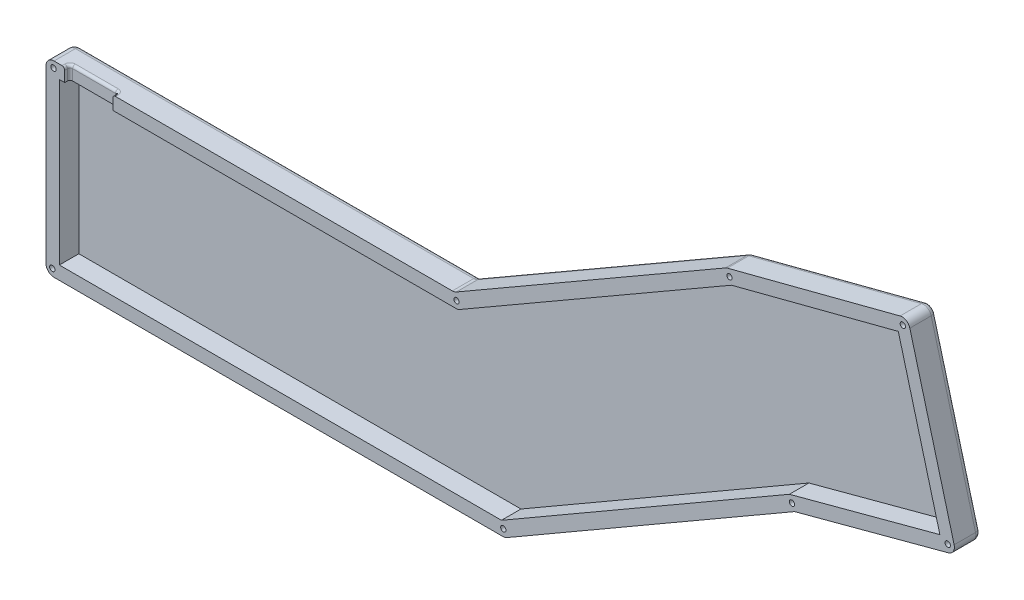
SolidWorks part; units mm, degrees
ref_plane "Plan de face" through (0, 0, 0) normal (0, 0, 1) x (1, 0, 0)
ref_plane "Plan de dessus" through (0, 0, 0) normal (0, 1, 0) x (1, 0, 0)
ref_plane "Plan de droite" through (0, 0, 0) normal (1, 0, 0) x (0, 0, -1)
sketch "Model" plane through (0, 0, 0) normal (0, 0, 1) x (1, 0, 0)
  line L0 (152.8114, 25.9717) -> (138.2826, 80.2215) construction
  line L1 (98.1506, 11.3316) -> (152.8114, 25.9717) construction
  line L2 (-9.3986, -50.8585) -> (98.1506, 11.3316) construction
  line L3 (-172.3739, -50.8585) -> (-9.3986, -50.8585) construction
  line L4 (-24.5886, 5.3017) -> (-172.3739, 5.2915) construction
  line L5 (138.2826, 80.2215) -> (78.0109, 64.5416) construction
  line L6 (-151.6088, 5.3124) -> (-151.6088, 5.2929)
  line L7 (-24.5886, 5.3017) -> (78.0109, 64.5416) construction
  line L8 (-172.3739, 5.2915) -> (-172.3739, -50.6876) construction
  line L9 (-172.3739, -50.6876) -> (-172.3739, -50.8585) construction
  line L10 (-25.1245, 7.3016) -> (-174.3739, 7.2914)
  line L11 (-174.3739, 7.2914) -> (-174.3739, -50.6876)
  line L12 (-174.3739, -50.6876) -> (-174.3739, -52.8585)
  line L13 (-174.3739, -52.8585) -> (-8.862, -52.8585)
  line L14 (-8.862, -52.8585) -> (98.9231, 9.4681)
  line L15 (98.9231, 9.4681) -> (155.2607, 24.5572)
  line L16 (155.2607, 24.5572) -> (139.7008, 82.657)
  line L17 (139.7008, 82.657) -> (77.2454, 66.409)
  line L18 (-25.1245, 7.3016) -> (77.2454, 66.409)
  line L19 (-26.4645, 12.3015) -> (-179.3739, 12.291)
  line L20 (-179.3739, 12.291) -> (-179.3739, -50.6876)
  line L21 (-179.3739, -50.6876) -> (-179.3739, -57.8585)
  line L22 (-179.3739, -57.8585) -> (-7.5204, -57.8585)
  line L23 (-7.5204, -57.8585) -> (100.8545, 4.8091)
  line L24 (100.8545, 4.8091) -> (161.3839, 21.021)
  line L25 (161.3839, 21.021) -> (143.2464, 88.7459)
  line L26 (143.2464, 88.7459) -> (75.3314, 71.0775)
  line L27 (-26.4645, 12.3015) -> (75.3314, 71.0775)
  circle A0 centre (80.6856, 58.4893) radius 1
  circle A1 centre (92.8776, 28.0855) radius 1
  circle A2 centre (-29.7028, -2.6485) radius 1
  circle A3 centre (-10.6528, -46.4381) radius 1
  circle A4 centre (-114.2594, -13.4181) radius 1
  circle A5 centre (-114.0308, -32.4935) radius 1
  dimension "D1" = 2
  dimension "D2" = 5
extrude "Boss.-Extru.1" add sketch "Model" along normal blind 10 contours L27 L19 L20 L21 L22 L23 L24 L25 L26 L10 L18 L17 L16 L15 L14 L13 L12 L11 region at (26.2883, 38.477, 0)
fillet "Congé1" radius 3 8 edges at (-26.4645, 12.3015, 5) (75.3314, 71.0775, 5) (143.2464, 88.7459, 5) (161.3839, 21.021, 5) (100.8545, 4.8091, 5) (-7.5204, -57.8585, 5) (-179.3739, -57.8585, 5) (-179.3739, 12.291, 5)
sketch "Esquisse1" plane through (0, 0, 0) normal (0, 0, 1) x (1, 0, 0)
  line L0 (-25.1245, 7.3016) -> (-174.3739, 7.2914) construction
  line L1 (-25.1245, 7.3016) -> (77.2454, 66.409) construction
  line L2 (139.7008, 82.657) -> (77.2454, 66.409) construction
  line L3 (155.2607, 24.5572) -> (139.7008, 82.657) construction
  line L4 (98.9231, 9.4681) -> (155.2607, 24.5572) construction
  line L5 (-8.862, -52.8585) -> (98.9231, 9.4681) construction
  line L6 (-174.3739, -52.8585) -> (-8.862, -52.8585) construction
  line L7 (-174.3739, -50.6876) -> (-174.3739, -52.8585) construction
  line L8 (-174.3739, 7.2914) -> (-174.3739, -50.6876) construction
  line L9 (-25.1245, 7.3016) -> (-174.3739, 7.2914)
  line L10 (-25.1245, 7.3016) -> (77.2454, 66.409)
  line L11 (139.7008, 82.657) -> (77.2454, 66.409)
  line L12 (155.2607, 24.5572) -> (139.7008, 82.657)
  line L13 (98.9231, 9.4681) -> (155.2607, 24.5572)
  line L14 (-8.862, -52.8585) -> (98.9231, 9.4681)
  line L15 (-174.3739, -52.8585) -> (-8.862, -52.8585)
  line L16 (-174.3739, -50.6876) -> (-174.3739, -52.8585)
  line L17 (-174.3739, 7.2914) -> (-174.3739, -50.6876)
extrude "Boss.-Extru.2" add sketch "Esquisse1" along normal blind 2.7
sketch "Esquisse3" plane through (0, 0, 0) normal (0, 0, 1) x (1, 0, 0)
  circle A0 centre (158.2016, 22.9581) radius 1
  circle A1 centre (141.3885, 85.5343) radius 1
  circle A2 centre (76.5002, 68.7766) radius 1
  circle A3 centre (99.8904, 7.0714) radius 1
  circle A4 centre (-8.1724, -55.2759) radius 1
  circle A5 centre (-25.6914, 9.9201) radius 1
  circle A6 centre (-176.5621, 9.9201) radius 1
  circle A7 centre (-177.0296, -55.2759) radius 1
sketch "Esquisse2" plane through (0, 0, 0) normal (0, 0, -1) x (-1, 0, 0)
  circle A0 centre (-80.6856, 58.4893) radius 1 construction
  circle A1 centre (-92.8776, 28.0855) radius 1 construction
  circle A2 centre (29.7028, -2.6485) radius 1 construction
  circle A3 centre (10.6528, -46.4381) radius 1 construction
  circle A4 centre (114.2594, -13.4181) radius 1 construction
  circle A5 centre (114.0308, -32.4935) radius 1 construction
  circle A6 centre (-80.6856, 58.4893) radius 1
  circle A7 centre (-92.8776, 28.0855) radius 1
  circle A8 centre (29.7028, -2.6485) radius 1
  circle A9 centre (10.6528, -46.4381) radius 1
  circle A10 centre (114.2594, -13.4181) radius 1
  circle A11 centre (114.0308, -32.4935) radius 1
  circle A12 centre (-80.6856, 58.4893) radius 2
  circle A13 centre (-92.8776, 28.0855) radius 2
  circle A14 centre (29.7028, -2.6485) radius 2
  circle A15 centre (10.6528, -46.4381) radius 2
  circle A16 centre (114.2594, -13.4181) radius 2
  circle A17 centre (114.0308, -32.4935) radius 2
  dimension "D1" = 1
fillet "Congé2" radius 2 16 edges at (100.8645, 4.785, 0) (46.844, -26.4224, 0) (-7.5479, -57.756, 0) (-92.3496, -57.8585, 0) (-178.4952, -56.9798, 0) (-179.3739, -22.7836, 0) (-178.4953, 11.4125, 0) (-101.8212, 12.2964, 0) (-26.4919, 12.4038, 0) (24.6056, 41.7889, 0) (75.3418, 71.0522, 0) (108.0441, 79.5878, 0) (142.6286, 87.6851, 0) (152.3124, 54.8937, 0) (160.3079, 21.6424, 0) (129.8616, 12.5782, 0)
extrude "Enlèv. mat.-Extru.1" cut sketch "Esquisse3" along normal blind 20
sketch "Esquisse4" plane through (0, 0, 0) normal (0, 0, -1) x (-1, 0, 0)
  circle A0 centre (177.0296, -55.2759) radius 2
  circle A1 centre (176.5621, 9.9201) radius 2
  circle A2 centre (25.6914, 9.9201) radius 2
  circle A3 centre (-76.5002, 68.7766) radius 2
  circle A4 centre (-141.3885, 85.5343) radius 2
  circle A5 centre (-158.2016, 22.9581) radius 2
  circle A6 centre (-99.8904, 7.0714) radius 2
  circle A7 centre (8.1724, -55.2759) radius 2
extrude "Enlèv. mat.-Extru.2" cut sketch "Esquisse4" against normal blind 2
sketch "Esquisse5" plane through (-0.0008, 12.3034, 0) normal (-0.0001, 1, 0) x (1, 0.0001, 0)
  line L0 (-27.2675, -2) -> (-176.3732, -2) construction
  line L1 (-171.3732, -8) -> (-155.3732, -8)
  line L2 (-172.3732, -9) -> (-172.3732, -18)
  line L3 (-172.3732, -18) -> (-154.3732, -18)
  line L4 (-154.3732, -9) -> (-154.3732, -18)
  line L5 (-176.3732, -2) -> (-176.3732, -10) construction
  arc A0 (-155.3732, -8) -> (-154.3732, -9) centre (-155.3732, -9) cw
  arc A1 (-171.3732, -8) -> (-172.3732, -9) centre (-171.3732, -9) ccw
  point P10 (-154.3732, -8)
  dimension "D4" = 1
  dimension "D1" = 6
  dimension "D2" = 4
  dimension "D3" = 10
  dimension "D5" = 18
extrude "Enlèv. mat.-Extru.3" cut sketch "Esquisse5" against normal blind 10
fillet "Congé3" radius 1 5 edges at (-154.3741, 12.2928, 9.5) (-154.667, 12.2927, 8.2929) (-172.3741, 12.2915, 9.5) (-172.0812, 12.2915, 8.2929) (-163.3741, 12.2921, 8)
